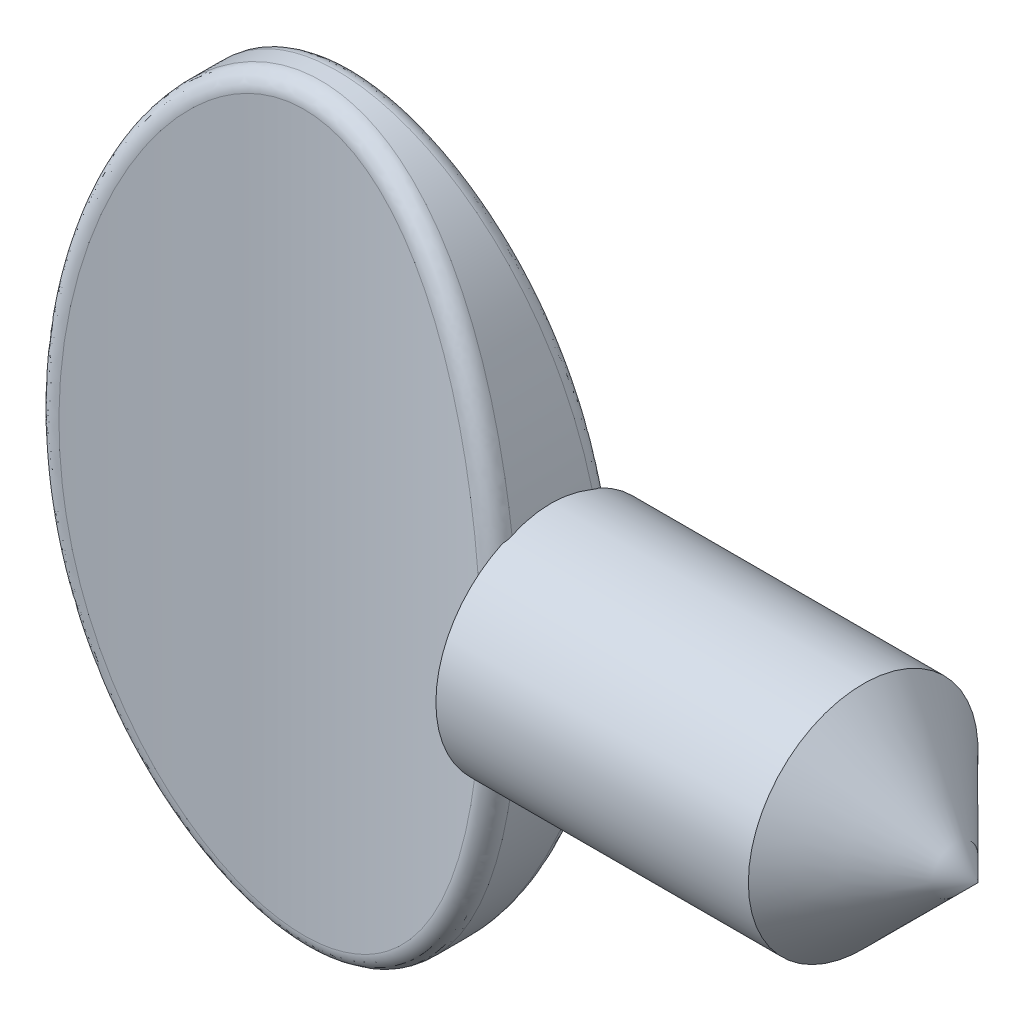
SolidWorks part; units mm, degrees
ref_plane "Front" through (0, 0, 0) normal (0, 0, 1) x (1, 0, 0)
ref_plane "Top" through (0, 0, 0) normal (0, 1, 0) x (1, 0, 0)
ref_plane "Right" through (0, 0, 0) normal (1, 0, 0) x (0, 0, -1)
ref_axis "Axis1" through (-50, 0, 0) along (1, 0, 0)
sketch "Sketch1" plane through (0, 0, 0) normal (0, 0, 1) x (1, 0, 0)
  line L0 (0, 0) -> (9.906, 0) construction
  line L1 (4.7413, -1.7526) -> (4.7413, 1.7526)
  line L2 (4.7413, -1.7526) -> (3.3847, -1.7526) construction
  ellipse E0 centre (0, 0) end of major axis (0, -5.715) minor radius 3.556
  dimension "D2" = 1.1853
  dimension "B" = 7.112
  dimension "L" = 6.35
extrude "Extrude1" add sketch "Sketch1" along normal mid plane 2.032
sketch "Sketch2" plane through (0, 0, 0) normal (0, 1, 0) x (1, 0, 0)
  line L0 (3.556, 1.016) -> (-3.556, 1.016) construction
  line L1 (0, 0) -> (0, 1.1721) construction
  line L2 (-1.7991, 0) -> (2.0444, 0) construction
  line L3 (-3.556, -1.016) -> (3.556, -1.016) construction
  line L6 (-3.556, 1.016) -> (-3.556, -1.016)
  line L7 (3.556, 1.016) -> (3.556, -1.016)
  arc A0 (-3.556, 1.016) -> (3.556, 1.016) centre (0, 10.6553) ccw
  arc A1 (-3.556, -1.016) -> (3.556, -1.016) centre (0, -10.6553) cw
extrude "Cut-Extrude1" cut sketch "Sketch2" against normal through all and the other way through all flip side to cut
fillet "Fillet3" radius 0.254 2 edges at (-3.4679, -1.2641, 0.984) (0.2073, 5.7053, -0.3831)
sketch "Sketch3" plane through (0, 0, 0) normal (0, 1, 0) x (1, 0, 0)
  line L0 (9.906, 0) -> (8.1534, 1.7526)
  line L1 (0, 0) -> (21.0288, 0) construction
  line L2 (0, 0) -> (9.906, 0) construction
  line L3 (4.7413, 1.7526) -> (4.7413, 0) construction
  line L4 (4.7413, 1.7526) -> (8.1534, 1.7526)
  line L6 (4.7413, 1.7526) -> (3.3847, 1.7526)
  line L7 (2.5775, 0.7096) -> (2.5775, 0)
  line L8 (3.3847, 0) -> (3.3847, 1.7526) construction
  line L9 (2.5775, 0) -> (9.906, 0)
  arc A0 (3.3847, 1.7526) -> (2.5775, 0.7096) centre (2.3072, 1.7526) cw
  arc A3 (-3.556, 1.016) -> (3.556, 1.016) centre (0, 10.6553) ccw construction
  dimension "D1" = 45
revolve "Revolve1" add sketch "Sketch3" angle 360 about L0
cosmetic thread "Cosmetic Thread1" [suppressed]
sketch "Sketch4" plane through (0, 0, 0) normal (0, 0, 1) x (1, 0, 0)
  line L0 (0, 0) -> (27.7993, 0) construction
  line L1 (7.9481, 1.7526) -> (8.1534, 1.397)
  line L2 (8.1534, 1.397) -> (8.3587, 1.7526)
  line L3 (8.3587, 1.7526) -> (8.3587, 2.1632)
  line L4 (8.3587, 2.1632) -> (7.9481, 2.1632)
  line L5 (7.9481, 2.1632) -> (7.9481, 1.7526)
  line L9 (8.1534, 1.7526) -> (8.1534, -1.7526) construction
  dimension "D1" = 2.794
  dimension "D2" = 3.5052
revolve "Cut-Revolve10" [suppressed] cut sketch "Sketch4" angle 360 about L0
pattern_linear "LPattern10" [suppressed] count 9 along (-1, 0, 0) of bodies 109
equation "\"D2@Sketch1\" = \"B@Sketch1\" / 6"
equation "\"D1@Fillet3\" = \"C1@Sketch2\" / 3"
equation "\"DIA@Sketch3\" = \"D@Sketch1\""
equation "\"D1@Cosmetic Thread1\" = \"L@Sketch1\" - \"D@Sketch1\" / 2"
equation "\"D1@Sketch4\" = \"D2@Cosmetic Thread1\""
equation "\"D2@Sketch4\" = \"DIA@Sketch3\""
equation "\"D1@LPattern10\" = \"D1@Cosmetic Thread1\" / \"P@LPattern10\" "
